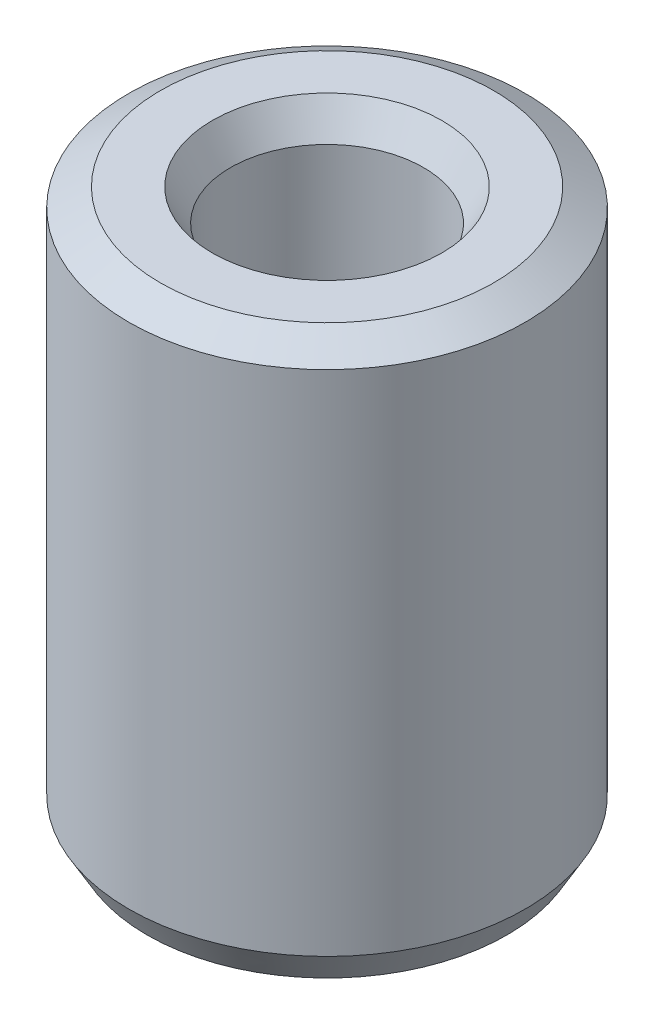
SolidWorks part; units mm, degrees
ref_plane "Front Plane" through (0, 0, 0) normal (0, 0, 1) x (1, 0, 0)
ref_plane "Top Plane" through (0, 0, 0) normal (0, 1, 0) x (1, 0, 0)
ref_plane "Right Plane" through (0, 0, 0) normal (1, 0, 0) x (0, 0, -1)
sketch "Sketch1" plane through (0, 0, 0) normal (0, 1, 0) x (1, 0, 0)
  circle A0 centre (0, 0) radius 37.5
  dimension "SLEEVE_OD" = 75
extrude "Boss-Extrude1" add sketch "Sketch1" along normal blind 105.5622
sketch "Sketch2" plane through (0, 0, 0) normal (0, 1, 0) x (1, 0, 0)
  circle A0 centre (0, 0) radius 18.2596
  dimension "BORE_D" = 36.5191
extrude "Cut-Extrude1" cut sketch "Sketch2" along normal through all
chamfer "Chamfer1" distance 3.4529 angle 60 4 edges at (0, 105.5622, 18.2596) (0, 0, 18.2596) (0, 0, 37.5) (0, 105.5622, 37.5) first distance on face at (0, 105.5622, 18.2596) first distance on face at (0, 0, 18.2596) first distance on face at (0, 105.5622, 37.5)
